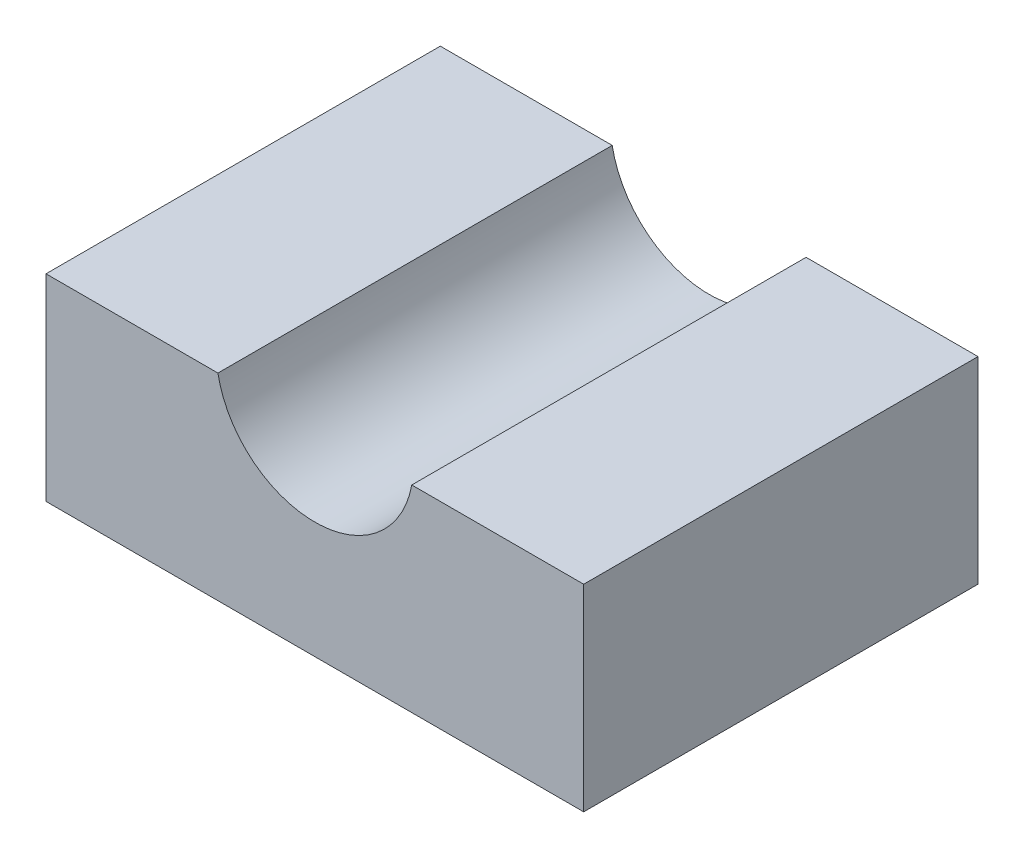
SolidWorks part; units mm, degrees
ref_plane "Front Plane" through (0, 0, 0) normal (0, 0, 1) x (1, 0, 0)
ref_plane "Top Plane" through (0, 0, 0) normal (0, 1, 0) x (1, 0, 0)
ref_plane "Right Plane" through (0, 0, 0) normal (1, 0, 0) x (0, 0, -1)
sketch "Sketch1" plane through (0, 0, 0) normal (0, 0, 1) x (1, 0, 0)
  line L0 (-15, 0) -> (15, 0) construction
  line L1 (0, 0) -> (0, -5.5) construction
  line L2 (-15, -1) -> (15, -1)
  line L4 (-15, -1) -> (-15, -12)
  line L5 (-15, -12) -> (15, -12)
  line L6 (15, -12) -> (15, -1)
  circle A0 centre (0, 0) radius 5.5
  dimension "D1" = 11
  dimension "D2" = 15
  dimension "D5" = 11
  dimension "D3" = 1
extrude "Boss-Extrude1" add sketch "Sketch1" along normal blind 22 contours A0 L2 L4 L5 L6 region at (0, -6.9509, 0)
